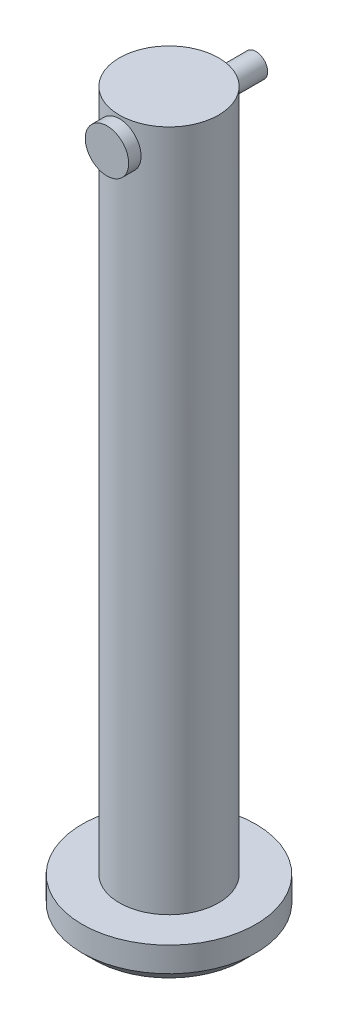
SolidWorks part; units mm, degrees
ref_plane "Front Plane" through (0, 0, 0) normal (0, 0, 1) x (1, 0, 0)
ref_plane "Top Plane" through (0, 0, 0) normal (0, 1, 0) x (1, 0, 0)
ref_plane "Right Plane" through (0, 0, 0) normal (1, 0, 0) x (0, 0, -1)
sketch "Sketch1" plane through (0, 0, 0) normal (0, 1, 0) x (1, 0, 0)
  circle A0 centre (0, 0) radius 4
extrude "Boss-Extrude1" add sketch "Sketch1" along normal blind 55
sketch "Sketch2" plane through (0, 0, 0) normal (0, -1, 0) x (1, 0, 0)
  circle A0 centre (0, 0) radius 7
  dimension "D1" = 14
extrude "Boss-Extrude2" add sketch "Sketch2" along normal blind 3
chamfer "Chamfer1" distance 1 angle 45 1 edges at (0, -3, -7)
sketch "Sketch3" plane through (0, 0, 0) normal (0, 0, 1) x (1, 0, 0)
  line L0 (4, 55) -> (-4, 55) construction
  circle A0 centre (0, 53) radius 1
  dimension "D1" = 2
  dimension "D2" = 2
extrude "Cut-Extrude1" cut sketch "Sketch3" against normal blind 10 and the other way blind 10
sketch "Sketch4" plane through (0, 0, 0) normal (0, 0, 1) x (1, 0, 0)
  circle A0 centre (0, 53) radius 0.95
  dimension "D1" = 1.9
extrude "Boss-Extrude3" add sketch "Sketch4" along normal blind 5 and the other way blind 7 separate body
sketch "Sketch5" plane through (0, 0, 5) normal (0, 0, 1) x (1, 0, 0)
  circle A0 centre (0, 53) radius 1.75
  dimension "D1" = 3.5
extrude "Boss-Extrude4" add sketch "Sketch5" against normal blind 1
